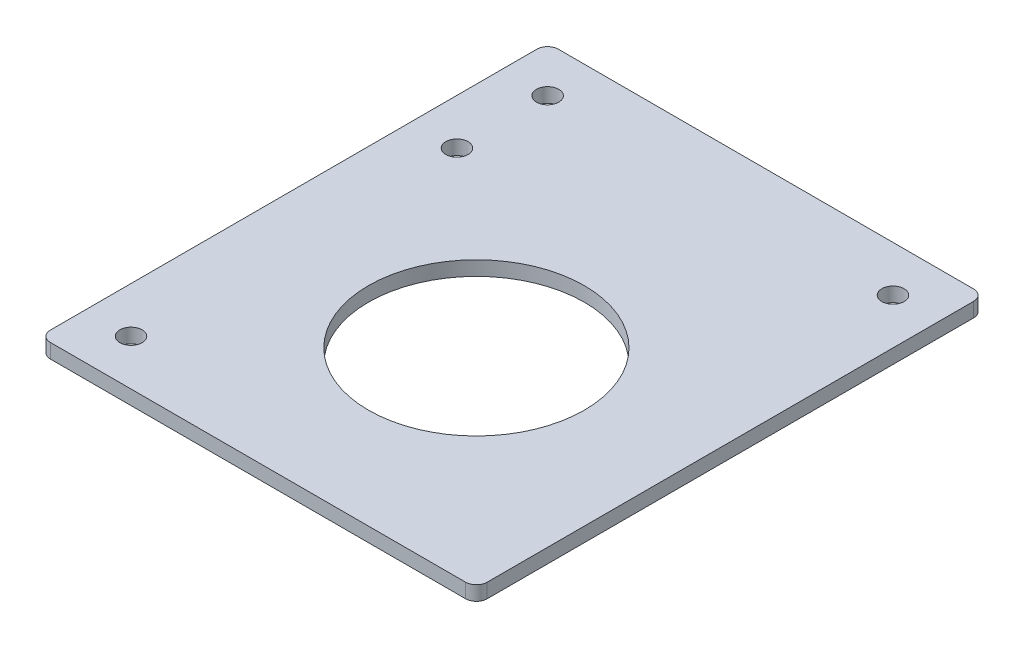
SolidWorks part; units mm, degrees
ref_plane "Front Plane" through (0, 0, 0) normal (0, 0, 1) x (1, 0, 0)
ref_plane "Top Plane" through (0, 0, 0) normal (0, 1, 0) x (1, 0, 0)
ref_plane "Right Plane" through (0, 0, 0) normal (1, 0, 0) x (0, 0, -1)
sketch "Sketch1" plane through (0, 0, 0) normal (0, 1, 0) x (1, 0, 0)
  line L0 (0.7175, -90.4) -> (88.7175, -90.4) construction
  line L1 (0.7175, 25.4) -> (122.1175, 25.4)
  line L3 (0.7175, -115.8) -> (122.1175, -115.8)
  line L4 (122.1175, 25.4) -> (122.1175, -115.8)
  line L5 (-27.2825, -90.4) -> (88.7175, -90.4) construction
  line L6 (88.7175, -90.4) -> (96.7175, -82.4) construction
  line L7 (96.7175, -82.4) -> (96.7175, -33.4) construction
  line L12 (96.7175, -33.4) -> (88.7175, -25.4) construction
  line L13 (88.7175, -25.4) -> (0.7175, -25.4) construction
  line L14 (88.7175, -25.4) -> (-27.2825, -25.4) construction
  line L16 (13.4175, 12.7) -> (0.7175, 12.7) construction
  line L17 (13.4175, 12.7) -> (13.4175, 25.4) construction
  line L18 (109.4175, 12.7) -> (109.4175, 25.4) construction
  line L19 (109.4175, 12.7) -> (122.1175, 12.7) construction
  line L20 (13.4175, -103.1) -> (0.7175, -103.1) construction
  line L21 (13.4175, -103.1) -> (13.4175, -100) construction
  line L22 (13.4175, -103.1) -> (13.4175, -115.8) construction
  line L23 (13.4175, 12.7) -> (16.5175, 12.7) construction
  line L24 (0.7175, -35.9) -> (16.9175, -35.9) construction
  line L25 (109.4175, 12.7) -> (109.4175, 9.6) construction
  line L30 (0.7175, 25.4) -> (0.7175, -115.8)
  line L31 (16.9175, -35.9) -> (-25.2825, -35.9) construction
  line L32 (13.4175, 12.7) -> (13.4175, -12.5) construction
  line L35 (-25.2825, -39.9) -> (16.9175, -39.9) construction
  line L36 (0.7175, -39.9) -> (16.9175, -39.9) construction
  line L37 (13.4175, -12.5) -> (16.5175, -12.5) construction
  circle A0 centre (64.2175, -57.9) radius 30
  circle A1 centre (13.4175, 12.7) radius 3.1
  circle A2 centre (109.4175, 12.7) radius 3.1
  circle A4 centre (13.4175, -103.1) radius 3.1
  arc A5 (16.9175, -39.9) -> (16.9175, -35.9) centre (16.9175, -37.9) ccw construction
  circle A6 centre (13.4175, -12.5) radius 3.1
  dimension "D4" = 60
  dimension "D5" = 88
  dimension "D6" = 6.2
  dimension "D1" = 50.8
  dimension "D2" = 25.4
  dimension "D3" = 25.4
  dimension "D7" = 12.7
  dimension "D8" = 25.2
extrude "Boss-Extrude1" add sketch "Sketch1" along normal blind 4
fillet "Fillet1" radius 3 4 edges at (122.1175, 2, -25.4) (122.1175, 2, 115.8) (0.7175, 2, 115.8) (0.7175, 2, -25.4)
